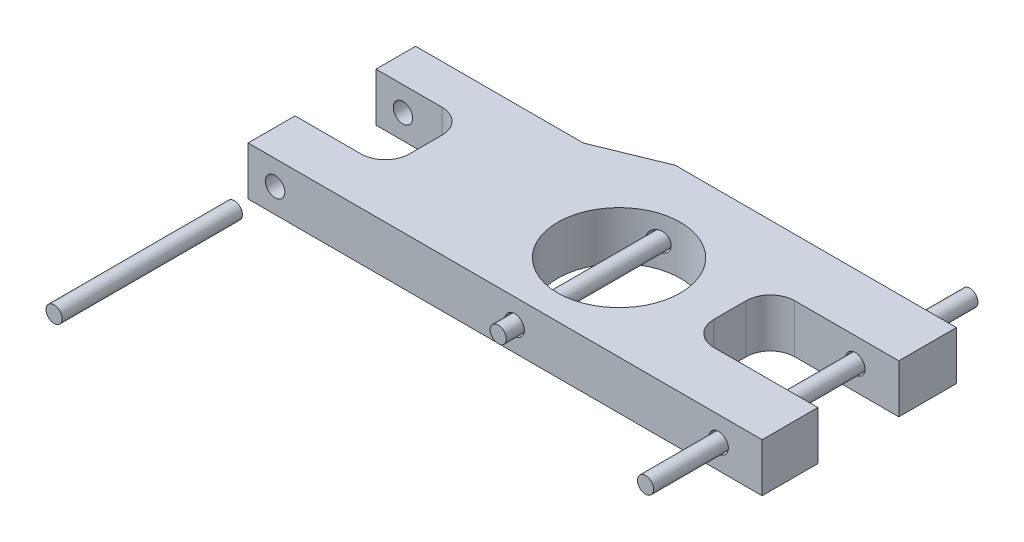
SolidWorks part; units mm, degrees
ref_plane "Front Plane" through (0, 0, 0) normal (0, 0, 1) x (1, 0, 0)
ref_plane "Top Plane" through (0, 0, 0) normal (0, 1, 0) x (1, 0, 0)
ref_plane "Right Plane" through (0, 0, 0) normal (1, 0, 0) x (0, 0, -1)
sketch "Sketch21" plane through (0, 0, 0) normal (0, 1, 0) x (1, 0, 0)
  line L0 (-68.3493, 26.4534) -> (-58.0049, 26.4534)
  line L1 (-54.1949, 22.6434) -> (-54.1949, 17.5634)
  line L2 (-58.0049, 13.7534) -> (-68.3493, 13.7534)
  line L3 (-68.3493, 13.7534) -> (-68.3493, 6.3892)
  line L4 (12.3038, 6.3892) -> (12.3038, 15.134)
  line L6 (-68.3493, 26.4534) -> (-68.3493, 32.6764)
  line L7 (12.3038, 27.834) -> (-4.0242, 27.834)
  line L8 (52.8639, 77.8829) -> (52.8639, -77.8829) construction
  line L9 (12.3038, 6.3892) -> (-68.3493, 6.3892)
  line L10 (-7.8342, 24.024) -> (-7.8342, 18.944)
  line L11 (-4.0242, 15.134) -> (12.3038, 15.134)
  line L12 (12.3038, 27.834) -> (12.3038, 36.8724)
  line L13 (0, 0) -> (-100.5945, 0) construction
  line L14 (-42.0395, 32.6764) -> (-31.7928, 36.8724)
  line L15 (-31.7928, 36.8724) -> (12.3038, 36.8724)
  line L17 (-68.3493, 32.6764) -> (-42.0395, 32.6764)
  line L18 (-100.5945, 0) -> (-100.5945, 33.0624) construction
  line L19 (-100.5945, 33.0624) -> (-78.14, 33.0624) construction
  circle A0 centre (-23.6637, 19.9075) radius 9.619
  circle A1 centre (-23.6637, 19.9075) radius 17.239 construction
  arc A6 (-58.0049, 26.4534) -> (-54.1949, 22.6434) centre (-58.0049, 22.6434) cw
  arc A7 (-54.1949, 17.5634) -> (-58.0049, 13.7534) centre (-58.0049, 17.5634) cw
  arc A8 (-4.0242, 27.834) -> (-7.8342, 24.024) centre (-4.0242, 24.024) ccw
  arc A9 (-7.8342, 18.944) -> (-4.0242, 15.134) centre (-4.0242, 18.944) ccw
  point P35 (-54.1949, 26.4534)
  point P38 (-54.1949, 13.7534)
  point P39 (-7.8342, 27.834)
  point P42 (-7.8342, 15.134)
  dimension "D7" = 7.62
  dimension "D5" = 3.81
  dimension "D6" = 33.0624
  dimension "D2" = 12.7
  dimension "D3" = 12.7
  dimension "D4" = 30.4831
  dimension "D8" = 6.223
  dimension "D10" = 6.3892
extrude "Extrude1" add sketch "Sketch21" along normal mid plane 7.62 contours L15 L12 L7 A8 L10 A9 L11 L4 L9 L3 L2 A7 L1 A6 L0 L6 L17 L14 | A0
sketch "Sketch22" plane through (0, 0, -36.8724) normal (0, 0, -1) x (-1, 0, 0)
  line L0 (29.6119, 0) -> (68.3493, 0) construction
  line L1 (29.6119, 3.81) -> (29.6119, -3.81) construction
  line L2 (68.3493, 3.81) -> (68.3493, -3.81) construction
  circle A0 centre (-5.4792, 0) radius 1.524
  circle A1 centre (64.1168, 0) radius 1.524
  circle A2 centre (26.5284, 0) radius 1.524
  dimension "D1" = 69.596
  dimension "D2" = 3.048
extrude "Cut-Extrude1" cut sketch "Sketch22" against normal mid plane 183.515
sketch "Sketch24" plane through (0, 0, 0) normal (0, 0, 1) x (1, 0, 0)
  circle A0 centre (-26.5284, 0) radius 1.27
  circle A1 centre (-64.1168, 0) radius 1.27
  circle A2 centre (5.4792, 0) radius 1.27
  dimension "D1" = 2.54
extrude "Extrude2" add sketch "Sketch24" against normal blind 34.29 from offset 3.81 separate body contours A0 offset against normal yes
extrude "Extrude3" add sketch "Sketch24<3>" along normal blind 28.288 separate body contours A1
sketch "Sketch24<3>" plane through (0, 0, 0) normal (0, 0, 1) x (1, 0, 0) same geometry as "Sketch24"
extrude "Extrude4" add sketch "Sketch24<4>" against normal blind 50.894 from offset 5.08 separate body contours A2
sketch "Sketch24<4>" plane through (0, 0, 0) normal (0, 0, 1) x (1, 0, 0) same geometry as "Sketch24"
